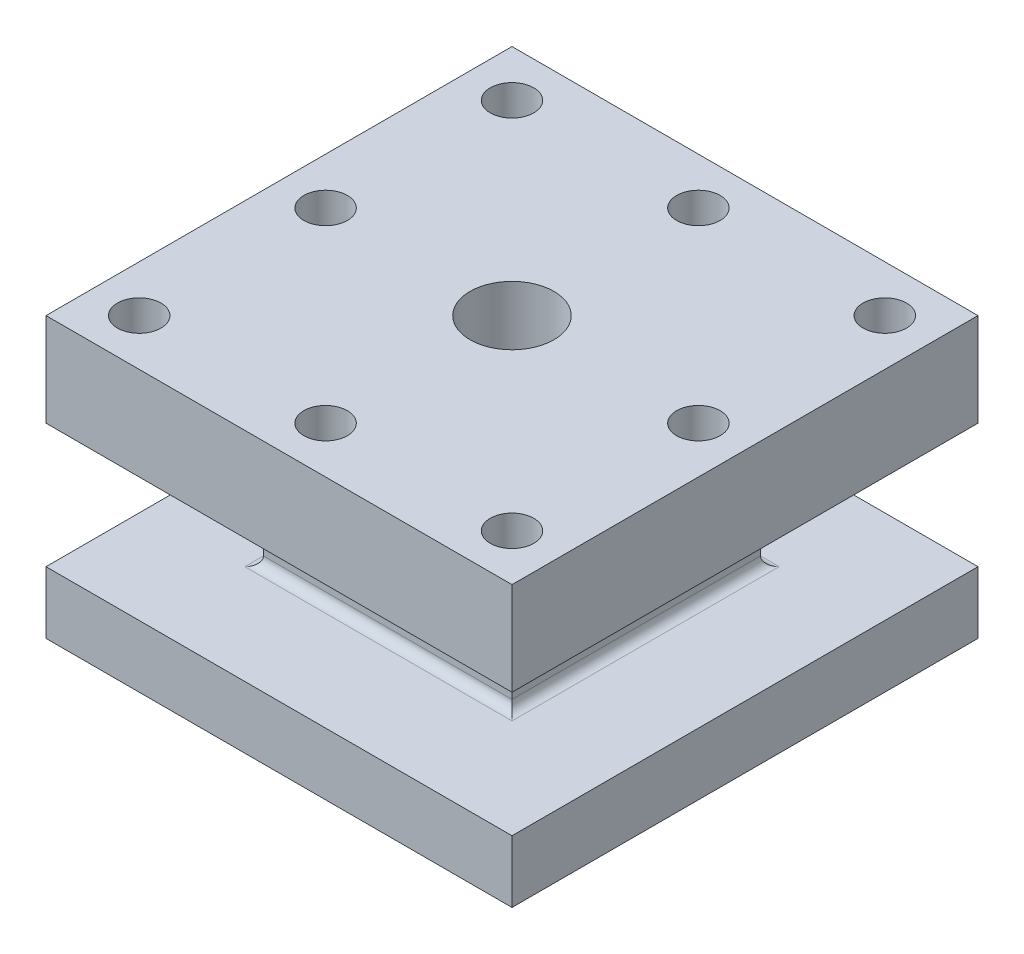
SolidWorks part; units mm, degrees
ref_plane "Front Plane" through (0, 0, 0) normal (0, 0, 1) x (1, 0, 0)
ref_plane "Top Plane" through (0, 0, 0) normal (0, 1, 0) x (1, 0, 0)
ref_plane "Right Plane" through (0, 0, 0) normal (1, 0, 0) x (0, 0, -1)
sketch "Sketch1" plane through (0, 0, 0) normal (0, 1, 0) x (1, 0, 0)
  line L1 (75, 75) -> (-75, 75)
  line L2 (75, 75) -> (75, -75)
  line L3 (75, -75) -> (-75, -75)
  line L4 (-75, 75) -> (-75, -75)
  line L5 (75, 75) -> (-75, -75) construction
  line L6 (75, -75) -> (-75, 75) construction
  point P0 (0, 0)
  dimension "D1" = 150
  dimension "D2" = 150
extrude "Boss-Extrude1" add sketch "Sketch1" against normal blind 30
sketch "Sketch2" plane through (0, -30, 0) normal (0, -1, 0) x (1, 0, 0)
  line L1 (40, 40) -> (-40, 40)
  line L2 (40, 40) -> (40, -40)
  line L3 (40, -40) -> (-40, -40)
  line L4 (-40, 40) -> (-40, -40)
  line L5 (40, 40) -> (-40, -40) construction
  line L6 (40, -40) -> (-40, 40) construction
  point P0 (0, 0)
  dimension "D1" = 80
  dimension "D2" = 80
extrude "Boss-Extrude2" add sketch "Sketch2" along normal blind 40
sketch "Sketch3" plane through (0, -70, 0) normal (0, -1, 0) x (1, 0, 0)
  line L4 (-75, -75) -> (75, -75)
  line L5 (-75, 75) -> (-75, -75)
  line L6 (75, 75) -> (-75, 75)
  line L7 (75, -75) -> (75, 75)
  line L8 (-75, -75) -> (75, -75)
  line L9 (-75, 75) -> (-75, -75)
  line L10 (75, 75) -> (-75, 75)
  line L11 (75, -75) -> (75, 75)
  dimension "D1" = 0
extrude "Boss-Extrude3" add sketch "Sketch3" along normal blind 20
hole_wizard "Hole1" positions "Sketch6" profile "Sketch7" legacy end condition through all
sketch "Sketch6" plane through (0, -90, 0) normal (0, -1, 0) x (-1, 0, 0)
  point P0 (0, 0)
  point P3 (0, 0)
sketch "Sketch7" plane through (0, -90, 0) normal (1, 0, 0) x (0, 0, -1)
  line L0 (0, 0) -> (0, 90)
  line L1 (0, 90) -> (13.5, 90)
  line L2 (13.5, 90) -> (13.5, 10)
  line L3 (13.5, 10) -> (30, 10)
  line L4 (30, 10) -> (30, 0)
  line L5 (30, 0) -> (0, 0)
  line L6 (0, 110) -> (0, -10) construction
  dimension "Diameter" = 27
  dimension "Depth" = 90
  dimension "C-Bore Diameter" = 60
  dimension "C-Bore Depth" = 10
hole_wizard "M16 Tapped Hole1" positions "Sketch8" profile "Sketch9" tap size "M16" standard "DIN" end condition up to next
sketch "Sketch8" plane through (0, 0, 0) normal (0, 1, 0) x (1, 0, 0)
  line L1 (60, 60) -> (-60, 60)
  line L2 (60, 60) -> (60, -60)
  line L3 (60, -60) -> (-60, -60)
  line L4 (-60, 60) -> (-60, -60) construction
  line L5 (60, 60) -> (-60, -60) construction
  line L6 (60, -60) -> (-60, 60) construction
  point P1 (0, 0)
  point P2 (-60, -60)
  point P189 (60, 60)
  point P190 (60, -60)
  point P191 (-60, 60)
  point P195 (0, 60)
  point P199 (60, 0)
  point P203 (0, -60)
  point P207 (-60, 0)
  dimension "D1" = 120
  dimension "D2" = 120
sketch "Sketch9" plane through (0, 0, 0) normal (1, 0, 0) x (0, 0, 1)
  line L0 (0, 0) -> (0, 90)
  line L1 (0, 90) -> (7, 90)
  line L2 (7, 90) -> (7, 0)
  line L5 (7, 0) -> (0, 0)
  line L11 (0, -6.35) -> (0, 107.95) construction
  dimension "Thru Tap Drill Dia." = 14
  dimension "Thru Tap Drill Depth" = 90
cosmetic thread "Hole Thread1" parameters "D2"=16
cosmetic thread "Hole Thread2" parameters "D2"=16
cosmetic thread "Hole Thread3" parameters "D2"=16
cosmetic thread "Hole Thread4" parameters "D2"=16
cosmetic thread "Hole Thread5" parameters "D2"=16
cosmetic thread "Hole Thread6" parameters "D2"=16
cosmetic thread "Hole Thread7" parameters "D2"=16
cosmetic thread "Hole Thread8" parameters "D2"=16
hole_wizard "Ø10.0 (10) Diameter Hole1" positions "Sketch10" profile "Sketch11" hole size "Ø10.0" standard "DIN"
sketch "Sketch10" plane through (0, -90, 0) normal (0, -1, 0) x (-1, 0, 0)
  line L1 (60, 60) -> (-60, 60)
  line L2 (60, 60) -> (60, -60)
  line L3 (60, -60) -> (-60, -60)
  line L4 (-60, 60) -> (-60, -60)
  line L5 (60, 60) -> (-60, -60) construction
  line L6 (60, -60) -> (-60, 60) construction
  point P1 (0, 0)
  point P161 (-60, 0)
  point P163 (60, 0)
  point P165 (0, 60)
  point P167 (0, -60)
  dimension "D1" = 120
  dimension "D2" = 120
sketch "Sketch11" plane through (0, -90, 0) normal (1, 0, 0) x (0, 0, -1)
  line L0 (0, 0) -> (0, 18)
  line L1 (0, 18) -> (5, 14.9957)
  line L2 (5, 14.9957) -> (5, 0)
  line L5 (5, 0) -> (0, 0)
  line L10 (0, 18) -> (-5, 14.9957) construction
  line L11 (0, -6.35) -> (0, 107.95) construction
  dimension "Hole Dia." = 10
  dimension "Hole Depth" = 18
  dimension "Drill Angle" = 118
fillet "Fillet1" radius 3 4 edges at (0, -70, -40) (-40, -70, 0) (0, -70, 40) (40, -70, 0)
chamfer "Chamfer1" distance 2 angle 45 1 edges at (0, -90, -30)
